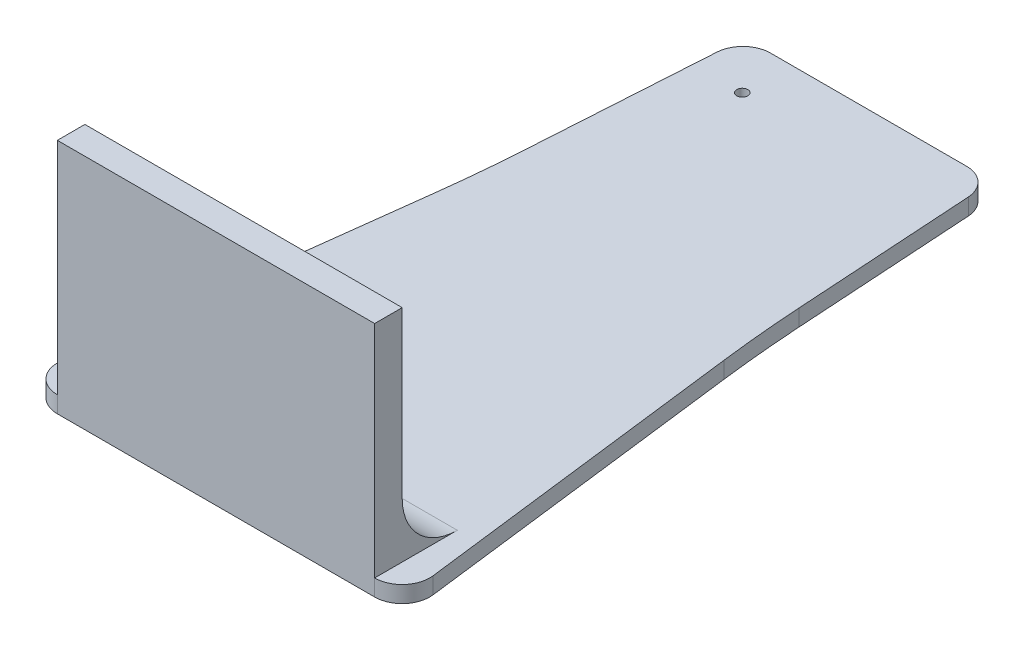
SolidWorks part; units mm, degrees
material "ABS"
ref_plane "Alzado" through (0, 0, 0) normal (0, 0, 1) x (1, 0, 0)
ref_plane "Planta" through (0, 0, 0) normal (0, 1, 0) x (1, 0, 0)
ref_plane "Vista lateral" through (0, 0, 0) normal (1, 0, 0) x (0, 0, -1)
sketch "Sketch1" plane through (0, 0, 0) normal (0, 1, 0) x (1, 0, 0)
  line L0 (0, -1000) -> (0, 49000) construction
  line L1 (-30, -30) -> (30, -30) construction
  line L2 (-30, -30) -> (-30, 30) construction
  line L3 (-30, 30) -> (30, 30) construction
  line L4 (30, -30) -> (30, 30) construction
  line L5 (-30, -30) -> (30, 30) construction
  line L6 (-30, 30) -> (30, -30) construction
  line L7 (-22.5, 7.5) -> (22.5, 7.5) construction
  line L8 (-22.5, 7.5) -> (-22.5, 52.5) construction
  line L9 (-22.5, 52.5) -> (22.5, 52.5)
  line L10 (22.5, 7.5) -> (22.5, 52.5) construction
  line L11 (-22.5, 7.5) -> (22.5, 52.5) construction
  line L12 (-22.5, 52.5) -> (22.5, 7.5) construction
  line L13 (-30, -65.9505) -> (30, -65.9505)
  line L14 (-30, -65.9505) -> (-30, -30) construction
  line L15 (-30, -30) -> (30, -30) construction
  line L17 (-30, -65.9505) -> (30, -30) construction
  line L18 (-30, -30) -> (30, -65.9505) construction
  line L19 (22.5, 52.5) -> (25.3493, 7.5)
  line L20 (25.3493, 7.5) -> (30, -30)
  line L21 (-30, -30) -> (-34.4174, -65.6187)
  line L22 (-22.5, 52.5) -> (-25.3493, 7.5)
  line L23 (30, -30) -> (34.4174, -65.6187)
  line L24 (27.5698, -27.5698) -> (30, -65.9505) construction
  line L25 (34.4174, -65.6187) -> (30, -65.9505)
  line L26 (-25.3493, 7.5) -> (-30, -30)
  line L27 (-34.4174, -65.6187) -> (-30, -65.9505)
  point P0 (0, 0)
  point P6 (0, 30)
  point P11 (0, -47.9753)
  dimension "D1" = 60
  dimension "D2" = 60
  dimension "D3" = 45
  dimension "D4" = 45
extrude "Boss-Extrude1" add sketch "Sketch1" along normal blind 3
fillet "Fillet1" radius 250 2 edges at (25.3493, 1.5, -7.5) (-25.3493, 1.5, -7.5)
fillet "Fillet2" radius 5 4 edges at (-22.5, 1.5, -52.5) (-34.4174, 1.5, 65.6187) (34.4174, 1.5, 65.6187) (22.5, 1.5, -52.5)
sketch "Sketch2" plane through (0, 3, 0) normal (0, 1, 0) x (1, 0, 0)
  line L1 (-14.1151, 27.7022) -> (14.1151, 27.7022) construction
  line L2 (-14.1151, 27.7022) -> (-14.1151, 43.7022) construction
  line L3 (-14.1151, 43.7022) -> (14.1151, 43.7022) construction
  line L4 (14.1151, 27.7022) -> (14.1151, 43.7022) construction
  line L5 (-14.1151, 27.7022) -> (14.1151, 43.7022) construction
  line L6 (-14.1151, 43.7022) -> (14.1151, 27.7022) construction
  circle A0 centre (-14.1151, 43.7022) radius 1
  point P0 (0, 35.7022)
  dimension "D1" = 2
  dimension "D2" = 16
extrude "Cut-Extrude1" cut sketch "Sketch2" against normal blind 3
sketch "Sketch3" plane through (0, 3, 0) normal (0, 1, 0) x (1, 0, 0)
  line L0 (-28.8001, -65.9505) -> (28.8001, -65.9505) construction
  line L1 (-28.8001, -65.9505) -> (28.8001, -65.9505)
  line L2 (-28.8001, -65.9505) -> (-28.8001, -60.9505)
  line L3 (-28.8001, -60.9505) -> (28.8001, -60.9505)
  line L4 (28.8001, -65.9505) -> (28.8001, -60.9505)
  arc A0 (-33.7621, -60.3352) -> (-28.8001, -65.9505) centre (-28.8001, -60.9505) ccw construction
extrude "Boss-Extrude2" add sketch "Sketch3" along normal blind 40
fillet "Fillet3" radius 10 1 edges at (0, 3, 60.9505)
